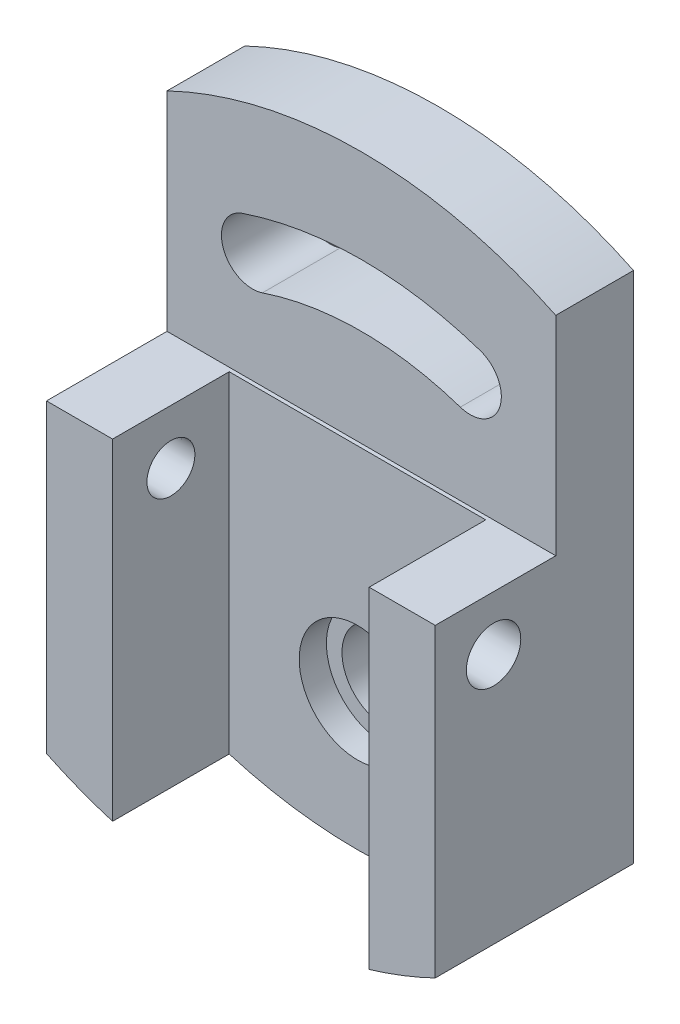
SolidWorks part; units mm, degrees
material "A286 Iron Base Superalloy"
ref_plane "Front Plane" through (0, 0, 0) normal (0, 0, 1) x (1, 0, 0)
ref_plane "Top Plane" through (0, 0, 0) normal (0, 1, 0) x (1, 0, 0)
ref_plane "Right Plane" through (0, 0, 0) normal (1, 0, 0) x (0, 0, -1)
sketch "Sketch1" plane through (0, 0, 0) normal (0, 0, 1) x (1, 0, 0)
  line L0 (0, 0) -> (0, 120) construction
  line L2 (-50, 108.5616) -> (-50, -23.5616)
  line L4 (50, 108.5616) -> (50, -23.5616)
  arc A0 (-50, 108.5616) -> (50, 108.5616) centre (0, 5) cw
  arc A1 (-50, -23.5616) -> (50, -23.5616) centre (0, 80) ccw
  point P0 (0, 0)
  dimension "D1" = 115
  dimension "D2" = 115
  dimension "D4" = 35
  dimension "D6" = 155
  dimension "D3" = 100
extrude "Boss-Extrude1" add sketch "Sketch1" along normal blind 20 contours L2 A1 L4 A0 region at (0, 42.5, 0)
sketch "Sketch2" plane through (0, 0, 20) normal (0, 0, 1) x (1, 0, 0)
  line L1 (-50, 108.5616) -> (-50, -23.5616) construction
  line L3 (-50, 55) -> (-50, -23.5616)
  line L4 (-50, 55) -> (-33, 55)
  line L5 (-33, 55) -> (-33, -30.1635)
  line L6 (0, -55) -> (0, 55) construction
  line L7 (33, 55) -> (33, -30.1635)
  line L8 (50, 55) -> (33, 55)
  line L9 (50, 55) -> (50, -23.5616)
  arc A0 (-50, -23.5616) -> (50, -23.5616) centre (0, 80) ccw construction
  arc A1 (-50, -23.5616) -> (-33, -30.1635) centre (0, 80) ccw
  arc A2 (50, -23.5616) -> (33, -30.1635) centre (0, 80) cw
  dimension "D1" = 90
  dimension "D2" = 33
extrude "Boss-Extrude2" add sketch "Sketch2" along normal blind 31
sketch "Sketch8" plane through (0, 0, 20) normal (0, 0, 1) x (1, 0, 0)
  circle A0 centre (0, 0) radius 15
  arc A1 (-33, -30.1635) -> (33, -30.1635) centre (0, 80) ccw construction
  circle A2 centre (0, 0) radius 11
  dimension "D2" = 30
  dimension "D3" = 22
  dimension "D1" = 35
extrude "Cut-Extrude4" cut sketch "Sketch8" against normal blind 6
extrude "Cut-Extrude5" cut sketch "Sketch8<2>" against normal through all contours A2 region at (0, 0, 20)
sketch "Sketch8<2>" plane through (0, 0, 20) normal (0, 0, 1) x (1, 0, 0) same geometry as "Sketch8"
sketch "Sketch9" plane through (50, 0, 0) normal (1, 0, 0) x (0, 0, -1)
  line L0 (-51, -23.5616) -> (-51, 55) construction
  line L1 (-51, 55) -> (-20, 55) construction
  circle A0 centre (-36, 41) radius 7
  dimension "D1" = 14
  dimension "D2" = 15
  dimension "D3" = 14
sketch "Sketch10" plane through (-50, 0, 0) normal (-1, 0, 0) x (0, 0, 1)
  circle A0 centre (36, 41) radius 6
  dimension "D1" = 12
loft "Cut-Loft1" cut profiles "Sketch10", "Sketch9" connector at (-50, 35.0005, 36.0792) connector at (50, 34.0109, 35.6088)
sketch "Sketch11" plane through (0, 0, 20) normal (0, 0, 1) x (1, 0, 0)
  line L0 (0, 88) -> (0, 0) construction
  arc A0 (-28, 83.4266) -> (28, 83.4266) centre (0, 0) cw construction
  arc A1 (30.5455, 91.0109) -> (-30.5455, 91.0109) centre (0, 0) ccw
  arc A2 (25.4545, 75.8424) -> (-25.4545, 75.8424) centre (0, 0) ccw
  arc A3 (25.4545, 75.8424) -> (30.5455, 91.0109) centre (28, 83.4266) ccw
  arc A4 (-30.5455, 91.0109) -> (-25.4545, 75.8424) centre (-28, 83.4266) ccw
  point P4 (0, 88)
  dimension "D1" = 88
  dimension "D3" = 8
  dimension "D2" = 56
extrude "Cut-Extrude6" cut sketch "Sketch11" against normal through all
sketch "Sketch12" plane through (0, 0, 20) normal (0, 0, 1) x (1, 0, 0)
  line L2 (-33, -30.1635) -> (-33, 55)
  line L3 (-33, 55) -> (33, 55)
  line L4 (33, -30.1635) -> (33, 55)
  circle A0 centre (0, 0) radius 11 construction
  circle A1 centre (0, 0) radius 15 construction
  circle A2 centre (0, 0) radius 11
  circle A3 centre (0, 0) radius 15
  arc A4 (-33, -30.1635) -> (33, -30.1635) centre (0, 80) ccw construction
  arc A5 (-33, -30.1635) -> (33, -30.1635) centre (0, 80) ccw
  circle M5 centre (0, 0) radius 15
  line M7 (-33, 55) -> (-33, -30.1635)
  arc M8 (-33, -30.1635) -> (33, -30.1635) centre (0, 80) ccw
  line M9 (33, -30.1635) -> (33, 55)
extrude "Boss-Extrude3" add sketch "Sketch12" along normal blind 1 contours L3 M7 M8 M9 M5 region at (-31.8839, 12.4182, 20)
